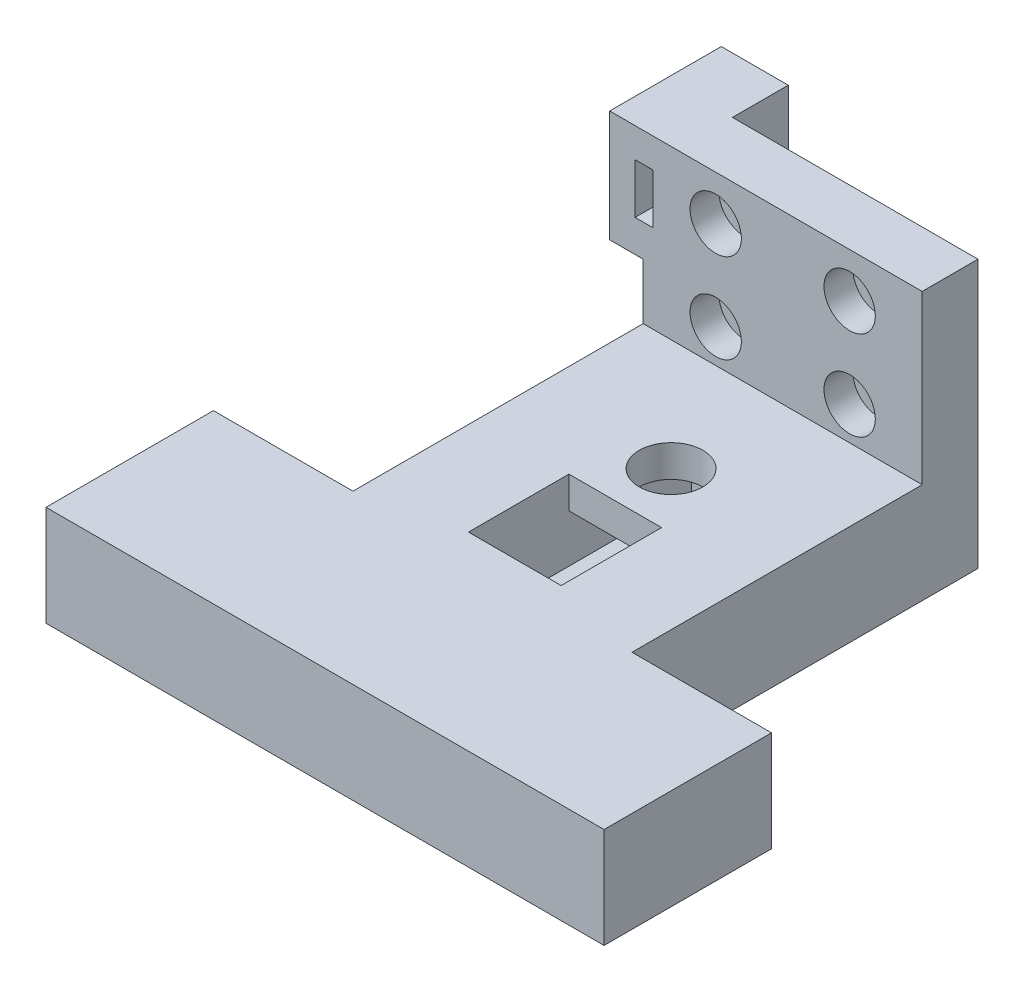
SolidWorks part; units mm, degrees
material "Brass"
ref_plane "Front Plane" through (0, 0, 0) normal (0, 0, 1) x (1, 0, 0)
ref_plane "Top Plane" through (0, 0, 0) normal (0, 1, 0) x (1, 0, 0)
ref_plane "Right Plane" through (0, 0, 0) normal (1, 0, 0) x (0, 0, -1)
sketch "Sketch1" plane through (0, 0, 0) normal (0, 0, 1) x (1, 0, 0)
  line L1 (0, 0) -> (25, 0)
  line L2 (0, 0) -> (0, 25)
  line L3 (0, 25) -> (25, 25)
  line L4 (25, 0) -> (25, 25)
  dimension "D1" = 25
  dimension "D2" = 25
extrude "Boss-Extrude1" add sketch "Sketch1" along normal blind 5
sketch "Sketch2" plane through (0, 0, 5) normal (0, 0, 1) x (1, 0, 0)
  line L0 (6.5, 21) -> (18.5, 21) construction
  line L1 (18.5, 21) -> (18.5, 13) construction
  line L2 (18.5, 13) -> (6.5, 13) construction
  line L3 (6.5, 13) -> (6.5, 21) construction
  line L4 (12.5, 25) -> (12.5, 21) construction
  line L5 (25, 25) -> (0, 25) construction
  dimension "D1" = 8
  dimension "D2" = 12
  dimension "D3" = 4
hole_wizard "CBORE for M2 SHCS1" positions "Sketch3" profile "Sketch4" counterbore size "M2" standard "ANSI Metric" end condition through all
sketch "Sketch3" plane through (0, 0, 5) normal (0, 0, 1) x (1, 0, 0)
  point P0 (6.5, 21)
  point P3 (18.5, 21)
  point P6 (18.5, 13)
  point P9 (6.5, 13)
sketch "Sketch4" plane through (6.5, 21, 5) normal (1, 0, 0) x (0, -1, 0)
  line L0 (0, 0) -> (0, 5)
  line L1 (0, 5) -> (1.3, 5)
  line L3 (1.3, 5) -> (1.3, 2.6)
  line L4 (1.3, 2.6) -> (2.3, 2.6)
  line L5 (2.3, 2.6) -> (2.3, 0)
  line L7 (2.3, 0) -> (0, 0)
  line L11 (0, -6.35) -> (0, 107.95) construction
  dimension "Thru Hole Dia." = 2.6
  dimension "Thru Hole Depth" = 5
  dimension "C'Bore Dia." = 4.6
  dimension "C'Bore Depth" = 2.6
sketch "Sketch5" plane through (0, 0, 5) normal (0, 0, 1) x (1, 0, 0)
  line L0 (0, 25) -> (0, 0) construction
  line L1 (0, 10) -> (25, 10)
  line L2 (0, 10) -> (0, 0)
  line L3 (0, 0) -> (25, 0)
  line L4 (25, 10) -> (25, 0)
  dimension "D1" = 10
extrude "Boss-Extrude2" add sketch "Sketch5" along normal blind 26
sketch "Sketch6" plane through (0, 10, 0) normal (0, 1, 0) x (1, 0, 0)
  line L0 (12.5, -5) -> (12.5, -15) construction
  line L1 (18.5, -5) -> (6.5, -5) construction
  circle A0 centre (12.5, -15) radius 2.85
  dimension "D1" = 5.7
  dimension "D2" = 10
extrude "Cut-Extrude1" cut sketch "Sketch6" against normal through all
sketch "Sketch7" plane through (0, 0, 31) normal (0, 0, 1) x (1, 0, 0)
  line L0 (12.5, 10) -> (12.5, 7.15) construction
  line L1 (8.35, 7.15) -> (16.65, 7.15)
  line L2 (8.35, 7.15) -> (8.35, 2.85)
  line L3 (8.35, 2.85) -> (16.65, 2.85)
  line L4 (16.65, 7.15) -> (16.65, 2.85)
  line L5 (25, 10) -> (0, 10) construction
  line L6 (25, 5) -> (16.65, 5) construction
  line L7 (25, 0) -> (25, 10) construction
  dimension "D1" = 4.3
  dimension "D2" = 8.3
extrude "Cut-Extrude2" cut sketch "Sketch7" against normal offset from surface (22 mm away) 9 up to face at (7.8, 21, 0)
sketch "Sketch8" plane through (0, 10, 0) normal (0, 1, 0) x (1, 0, 0)
  line L0 (16.65, -9) -> (16.65, -31) construction
  line L1 (8.35, -29) -> (16.65, -29)
  line L2 (8.35, -29) -> (8.35, -20)
  line L3 (8.35, -20) -> (16.65, -20)
  line L4 (16.65, -29) -> (16.65, -20)
  line L5 (25, -31) -> (0, -31) construction
  line L6 (12.5, -15) -> (12.5, -20) construction
  dimension "D1" = 9
  dimension "D2" = 2
extrude "Cut-Extrude3" cut sketch "Sketch8" against normal up to surface (2.85 mm away) up to face at (12.5, 7.15, 20)
extrude "Boss-Extrude5" add sketch "Sketch7<2>" against normal up to surface (2 mm away) up to face at (12.5, 8.575, 29)
sketch "Sketch7<2>" plane through (0, 0, 31) normal (0, 0, 1) x (1, 0, 0) same geometry as "Sketch7"
sketch "Sketch9" plane through (0, 0, 31) normal (0, 0, 1) x (1, 0, 0)
  line L0 (12.5, 25) -> (12.5, 10) construction
  line L1 (-12.5, 10) -> (37.5, 10)
  line L2 (-12.5, 10) -> (-12.5, 0)
  line L3 (-12.5, 0) -> (37.5, 0)
  line L4 (37.5, 10) -> (37.5, 0)
  line L5 (25, 10) -> (0, 10) construction
  line L6 (0, 0) -> (25, 0) construction
  dimension "D1" = 50
extrude "Boss-Extrude3" add sketch "Sketch9" along normal blind 20
ref_plane "Plane1" through (12.5, 0, 0) normal (1, 0, 0) x (0, 0, -1)
sketch "Sketch10" plane through (0, 10, 0) normal (0, 1, 0) x (1, 0, 0)
  line L0 (37.5, -51) -> (37.5, -31) construction
  line L1 (-12.5, -51) -> (37.5, -51)
  line L2 (-12.5, -51) -> (-12.5, -44)
  line L3 (-12.5, -44) -> (37.5, -44)
  line L4 (37.5, -51) -> (37.5, -44)
  dimension "D1" = 7
extrude "Cut-Extrude4" cut sketch "Sketch10" against normal through all
sketch "Sketch11" plane through (0, 0, 0) normal (-1, 0, 0) x (0, 0, 1)
  line L0 (31, 0) -> (0, 0) construction
  line L1 (0, 25) -> (5, 25)
  line L2 (0, 25) -> (0, 0)
  line L3 (0, 0) -> (5, 0)
  line L4 (5, 25) -> (5, 0)
  line L5 (5, 25) -> (5, 10) construction
extrude "Boss-Extrude6" add sketch "Sketch11" along normal blind 3
sketch "Sketch12" plane through (0, 0, 5) normal (0, 0, 1) x (1, 0, 0)
  line L1 (-3, 0) -> (0, 0)
  line L2 (-3, 0) -> (-3, 15)
  line L3 (-3, 15) -> (0, 15)
  line L4 (0, 0) -> (0, 15)
  dimension "D1" = 15
extrude "Cut-Extrude5" cut sketch "Sketch12" against normal through all
sketch "Sketch13" plane through (0, 0, 0) normal (0, 0, -1) x (-1, 0, 0)
  line L1 (-3, 15) -> (3, 15)
  line L2 (-3, 15) -> (-3, 25)
  line L3 (-3, 25) -> (3, 25)
  line L4 (3, 15) -> (3, 25)
  dimension "D1" = 6
extrude "Boss-Extrude7" add sketch "Sketch13" along normal blind 5
sketch "Sketch14" plane through (0, 0, 5) normal (0, 0, 1) x (1, 0, 0)
  line L0 (25, 25) -> (-3, 25) construction
  line L1 (-0.52, 22.16) -> (0.699, 22.16)
  line L2 (-0.52, 22.16) -> (-0.52, 18.08)
  line L3 (-0.52, 18.08) -> (0.699, 18.08)
  line L4 (0.699, 22.16) -> (0.699, 18.08)
  line L5 (-3, 15) -> (-3, 25) construction
  dimension "D1" = 2.84
  dimension "D2" = 2.48
  dimension "D3" = 4.08
  dimension "D4" = 1.219
extrude "Cut-Extrude6" cut sketch "Sketch14" against normal through all
sketch "Sketch15" plane through (0, 0, 5) normal (0, 0, 1) x (1, 0, 0)
  line L9 (-0.72, 17.88) -> (0.899, 17.88)
  line L10 (-0.72, 22.36) -> (-0.72, 17.88)
  line L11 (0.899, 22.36) -> (-0.72, 22.36)
  line L12 (0.899, 17.88) -> (0.899, 22.36)
  line L13 (-0.72, 17.88) -> (0.899, 17.88)
  line L14 (-0.72, 22.36) -> (-0.72, 17.88)
  line L15 (0.899, 22.36) -> (-0.72, 22.36)
  line L16 (0.899, 17.88) -> (0.899, 22.36)
  dimension "D1" = 0.2
extrude "Cut-Extrude7" cut sketch "Sketch15" against normal through all
sketch "Sketch16" plane through (0, 0, 44) normal (0, 0, 1) x (1, 0, 0)
  line L4 (37.5, 10) -> (-12.5, 10)
  line L5 (-12.5, 10) -> (-12.5, 0)
  line L6 (-12.5, 0) -> (37.5, 0)
  line L7 (37.5, 0) -> (37.5, 10)
  line L8 (37.5, 10) -> (-12.5, 10)
  line L9 (-12.5, 10) -> (-12.5, 0)
  line L10 (-12.5, 0) -> (37.5, 0)
  line L11 (37.5, 0) -> (37.5, 10)
  dimension "D1" = 0
extrude "Boss-Extrude8" add sketch "Sketch16" along normal blind 2
chamfer "Chamfer1" distance 1 angle 45 8 edges at (-6.25, 0, 31) (0, 0, 15.5) (12.5, 0, 0) (25, 0, 15.5) (31.25, 0, 31) (37.5, 0, 38.5) (-12.5, 0, 38.5) (12.5, 0, 46)
